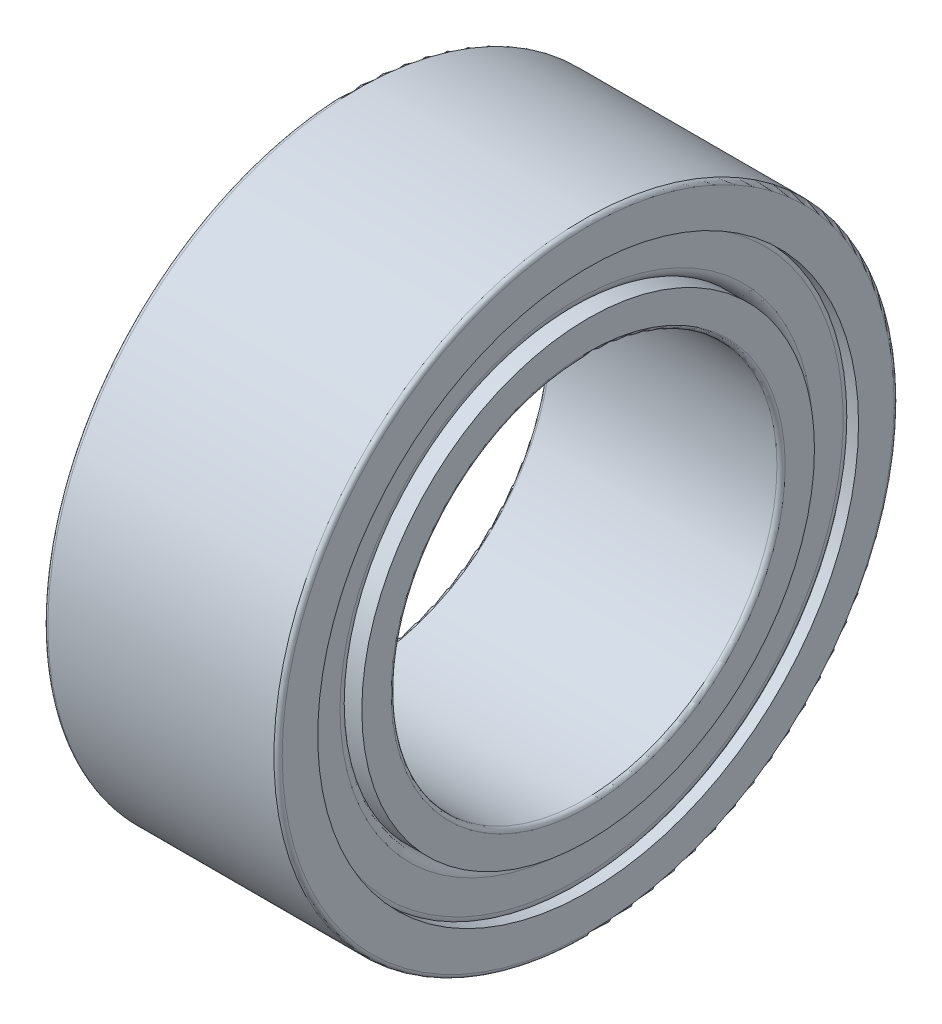
SolidWorks part; units mm, degrees
ref_plane "Plane1" through (0, 0, 0) normal (0, 0, 1) x (1, 0, 0)
ref_plane "Plane2" through (0, 0, 0) normal (0, 1, 0) x (1, 0, 0)
ref_plane "Plane3" through (0, 0, 0) normal (1, 0, 0) x (0, 0, -1)
other "Configuration Table"
sketch "Clipboard" plane through (0, 0, 0) normal (0, 0, 1) x (1, 0, 0)
  line L0 (-10, 0) -> (10, 0) construction
  line L1 (0, 0) -> (32.825, -1.1463)
  line L2 (0, 0) -> (36.4778, 1.2738)
  line L3 (0, 0) -> (40.1305, -1.4014)
  line L4 (0, 0) -> (-22.3573, -0.3902)
sketch "OutRacSke" plane through (0, 0, 0) normal (0, 0, 1) x (1, 0, 0)
  line L0 (-7.65, 20.0775) -> (-7.65, 19.6206)
  line L1 (-7.65, 19.6206) -> (-8.5, 19.6206)
  line L2 (-8.5, 19.6206) -> (-8.5, 22.2)
  line L3 (-8.2, 22.5) -> (8.2, 22.5)
  line L4 (8.5, 22.2) -> (8.5, 19.6206)
  line L5 (8.5, 19.6206) -> (7.65, 19.6206)
  line L6 (7.65, 19.6206) -> (7.65, 20.0775)
  line L7 (7.65, 20.0775) -> (-7.65, 20.0775)
  line L8 (-7.9375, 0) -> (7.9375, 0) construction
  arc A0 (-8.5, 22.2) -> (-8.2, 22.5) centre (-8.2, 22.2) cw
  arc A1 (8.2, 22.5) -> (8.5, 22.2) centre (8.2, 22.2) cw
  dimension "D1" = 7.65
  dimension "Groove_Dp" = 0.4569
  dimension "Cyl_Len" = 15.3
  dimension "halfWidth" = 8.5
revolve "OuterRace" add sketch "OutRacSke" angle 360 about L8 reverse direction yes
sketch "RolDetSke" plane through (0, 0, 0) normal (0, 0, 1) x (1, 0, 0)
  line L0 (-7.65, 19.3468) -> (-7.65, 18.25)
  line L1 (-7.65, 18.25) -> (7.65, 18.25)
  line L2 (7.65, 18.25) -> (7.65, 19.3468)
  line L3 (6.9188, 20.078) -> (-6.9188, 20.078)
  line L4 (-28.575, 18.25) -> (28.575, 18.25) construction
  arc A0 (7.65, 19.3468) -> (6.9188, 20.078) centre (6.9188, 19.3468) ccw
  arc A1 (-6.9188, 20.078) -> (-7.65, 19.3468) centre (-6.9188, 19.3468) ccw
  dimension "Cyl_Len" = 15.3
  dimension "radius" = 0.7312
  dimension "Roller_diameter" = 3.656
revolve "RollerDetailed" [suppressed] add sketch "RolDetSke" angle 360 about L4 reverse direction yes
ref_axis "Axis1" through (-50, 0, 0) along (1, 0, 0)
sketch "RolSimSke" plane through (0, 25.4, 0) normal (0, 0, 1) x (1, 0, 0)
  line L0 (-7.65, -6.0527) -> (-7.65, -8.2463)
  line L1 (-25.4, -25.4) -> (25.4, -25.4) construction
  line L2 (7.65, -8.2463) -> (7.65, -6.0527)
  line L3 (6.9188, -5.3215) -> (-6.9188, -5.3215)
  line L5 (6.9188, -8.9775) -> (-6.9188, -8.9775)
  arc A0 (7.65, -6.0527) -> (6.9188, -5.3215) centre (6.9188, -6.0527) ccw
  arc A1 (-6.9188, -5.3215) -> (-7.65, -6.0527) centre (-6.9188, -6.0527) ccw
  arc A2 (7.65, -8.2463) -> (6.9188, -8.9775) centre (6.9188, -8.2463) cw
  arc A3 (-6.9188, -8.9775) -> (-7.65, -8.2463) centre (-6.9188, -8.2463) cw
  dimension "Cyl_Len" = 15.3
  dimension "radius" = 0.7312
  dimension "Roller_diameter" = 3.656
revolve "RollersSimplified" add sketch "RolSimSke" angle 360 about L1
sketch "InsRacSke" plane through (0, 0, 0) normal (0, 0, 1) x (1, 0, 0)
  line L2 (-8.5, 16.4225) -> (-8.5, 14.3)
  line L4 (-8.2, 14) -> (8.2, 14)
  line L5 (8.5, 14.3) -> (8.5, 16.4225)
  line L8 (8.5, 16.4225) -> (-8.5, 16.4225)
  line L9 (-7.9375, 0) -> (7.9375, 0) construction
  arc A0 (-8.5, 14.3) -> (-8.2, 14) centre (-8.2, 14.3) ccw
  arc A2 (8.2, 14) -> (8.5, 14.3) centre (8.2, 14.3) ccw
  dimension "radius" = 0.3
  dimension "halfWidth" = 8.5
revolve "InnerRace" add sketch "InsRacSke" angle 360 about L9 reverse direction yes
sketch "CagSpiSke" plane through (0, 0, 0) normal (0, 0, 1) x (1, 0, 0)
  line L0 (-17.1595, 0) -> (17.1595, 0) construction
  line L3 (-8.075, 17.8844) -> (8.075, 17.8844)
  line L4 (-8.075, 17.8844) -> (-8.075, 18.6156)
  line L5 (-8.075, 18.6156) -> (8.075, 18.6156)
  line L6 (8.075, 17.8844) -> (8.075, 18.6156)
revolve "CageSpine" [suppressed] add sketch "CagSpiSke" angle 0.001 about L0
pattern_circular "RollersDetailed" [suppressed] count 2 every 180 about axis through (-50, 0, 0) along (1, 0, 0)
equation "\"halfWidth@OutRacSke\" =  \"Width@OutRacSke\" / 2"
equation "\"CLdia@Clipboard\" =  ( \"Race_OD@Clipboard\" + \"Race_ID@Clipboard\" )  / 2"
equation "\"CLRad@RolDetSke\" = ( \"Race_OD@Clipboard\" + \"Race_ID@Clipboard\" )  / 4"
equation "\"Roller_diameter@RolDetSke\" =  ( \"Race_OD@Clipboard\" -  \"Race_ID@Clipboard\" )  / 2 + .001"
equation "\"Roller_diameter@RolSimSke\" = ( \"Race_OD@Clipboard\" -  \"Race_ID@Clipboard\" )  / 2 + .001"
equation "\"radius@RolDetSke\" = \"Roller_diameter@RolDetSke\" / 5"
equation "\"radius@RolSimSke\" = \"Roller_diameter@RolSimSke\" / 5"
equation "\"Cyl_Len@OutRacSke\" = \"Cyl_Len@RolDetSke\""
equation "\"Cyl_Len@RolSimSke\" = \"Cyl_Len@RolDetSke\""
equation "\"halfCylLen@RolDetSke\" = \"Cyl_Len@RolDetSke\" / 2"
equation "\"D1@OutRacSke\" = \"Cyl_Len@OutRacSke\" / 2"
equation "\"cage_width@CagSpiSke\" =  ( \"Cyl_Len@RolDetSke\" + \"Width@OutRacSke\" )  / 2"
equation "\"halfwidth@CagSpiSke\" = \"cage_width@CagSpiSke\" / 2"
equation "\"cage_thickness@CagSpiSke\" = \"Roller_diameter@RolDetSke\" / 5"
equation "\"d2@CagSpiSke\" = \"CLRad@RolDetSke\" * 2 - \"cage_thickness@CagSpiSke\""
equation "\"Max_count@Clipboard\" = int( 3.14159265 / atn(( \"Roller_diameter@RolDetSke\" / 2) / sqr( \"CLRad@RolDetSke\"  *  \"CLRad@RolDetSke\" - ( \"Roller_diameter@RolDetSke\" / 2) *  ( \"Roller_diameter@RolDetSke\" / 2))))"
equation "\"Max_count@Clipboard\" = ((sgn( \"Max_count@Clipboard\" - \"Count@Clipboard\" )-1)*( \"Max_count@Clipboard\" - \"Count@Clipboard\" ))/-2+ \"Count@Clipboard\""
equation "\"Count@RollersDetailed\" = int( \"Show_count@Clipboard\" ) "
equation "\"Count@RollersDetailed\" = ((sgn( \"Count@RollersDetailed\" - \"Max_count@Clipboard\" )-1)*( \"Count@RollersDetailed\" - \"Max_count@Clipboard\" ))/-2+ \"Max_count@Clipboard\""
equation "\"Count@RollersDetailed\" = ((sgn( \"Count@RollersDetailed\" - \"Min_count@Clipboard\" )+1)*( \"Count@RollersDetailed\" - \"Min_count@Clipboard\"))/2 +\"Min_count@Clipboard\""
equation "\"Angle@RollersDetailed\" = 360.0 / \"Max_count@Clipboard\""
equation "\"Bore@RolSimSke\" = \"Race_ID@Clipboard\""
equation "\"Race_ID@InsRacSke\" = \"Race_ID@Clipboard\""
equation "\"halfWidth@InsRacSke\" = \"Width_IR@InsRacSke\" / 2"
equation "\"halfLength@RolSimSke\" = \"Cyl_Len@RolSimSke\" / 2"
equation "\"Race_OD@OutRacSke\" = \"Race_OD@Clipboard\""
equation "\"Width_IR@InsRacSke\" = \"Width@OutRacSke\""
equation "\"Angle@CageSpine\" =  \"Angle@RollersDetailed\" * ( \"Count@RollersDetailed\" -1 + int( \"Count@RollersDetailed\" / \"Max_count@Clipboard\" ) )  + 0.001 -  int( \"Count@RollersDetailed\" / \"Max_count@Clipboard\" ) * 0.001"
equation "\"Angle@CageSpine\" =  \"Angle@CageSpine\" * int( \"Min_count@Clipboard\" / 2) + int(1 / \"Min_count@Clipboard\")  * 0.001"
equation "\"radius@InsRacSke\" = \"Radius@OutRacSke\""
